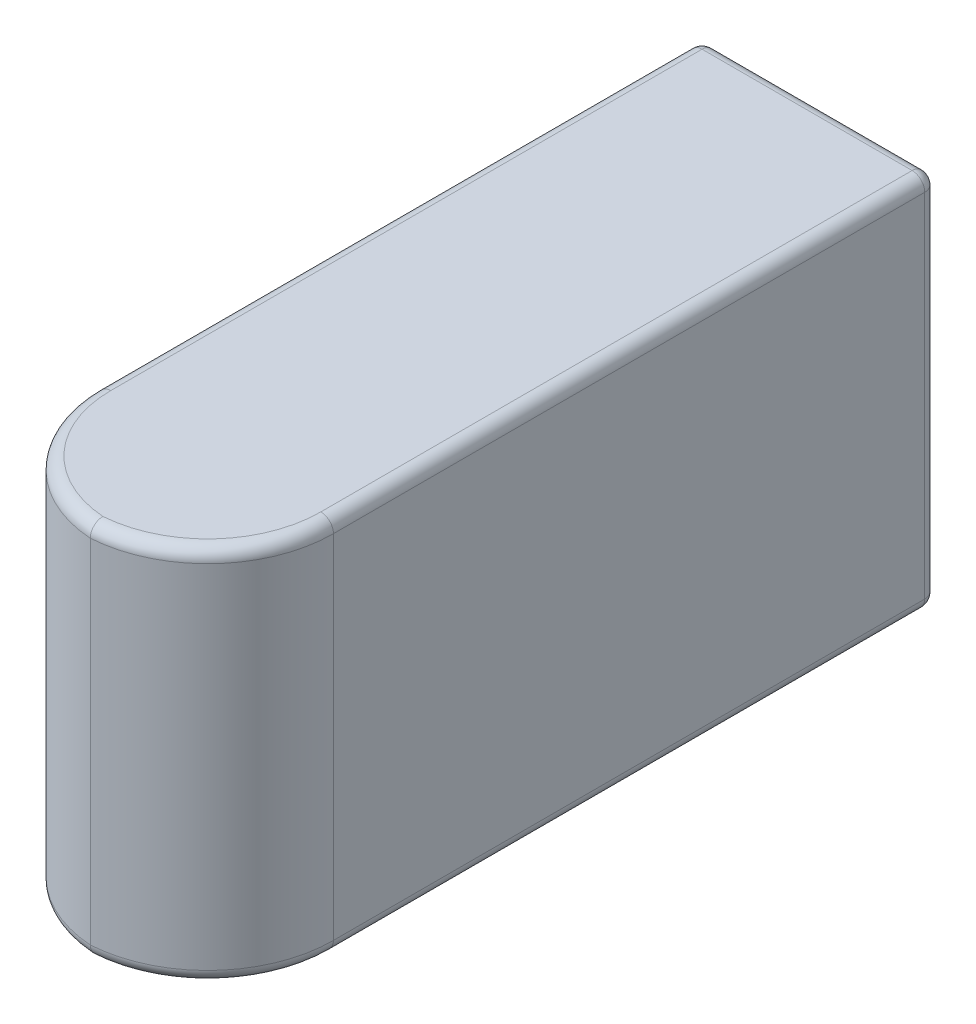
SolidWorks part; units mm, degrees
ref_plane "Front Plane" through (0, 0, 0) normal (0, 0, 1) x (1, 0, 0)
ref_plane "Top Plane" through (0, 0, 0) normal (0, 1, 0) x (1, 0, 0)
ref_plane "Right Plane" through (0, 0, 0) normal (1, 0, 0) x (0, 0, -1)
sketch "Sketch2" plane through (0, 0, 0) normal (1, 0, 0) x (0, 0, -1)
  line L1 (-29, 15) -> (29, 15)
  line L2 (-29, 15) -> (-29, -15)
  line L3 (-29, -15) -> (29, -15)
  line L4 (29, 15) -> (29, -15)
  line L5 (-29, 15) -> (29, -15) construction
  line L6 (-29, -15) -> (29, 15) construction
  point P0 (0, 0)
  dimension "D1" = 58
  dimension "D2" = 30
extrude "Boss-Extrude1" add sketch "Sketch2" along normal blind 18.7 contours L2 L3 L4 L1
fillet "Fillet1" radius 10 2 edges at (0, 0, 29) (18.7, 0, 29)
fillet "Fillet2" radius 1 12 edges at (2.7027, 15, 25.8374) (2.7027, -15, 25.8374) (15.9973, -15, 25.8374) (15.9973, 15, 25.8374) (0, 15, -5) (0, -15, -5) (18.7, -15, -5) (18.7, 15, -5) (9.35, -15, -29) (18.7, 0, -29) (9.35, 15, -29) (0, 0, -29)
sketch "Sketch4" plane through (18.7, 0, 0) normal (1, 0, 0) x (0, 0, -1)
  line L0 (-44.4392, -29.076) -> (110.2275, -29.076) construction
